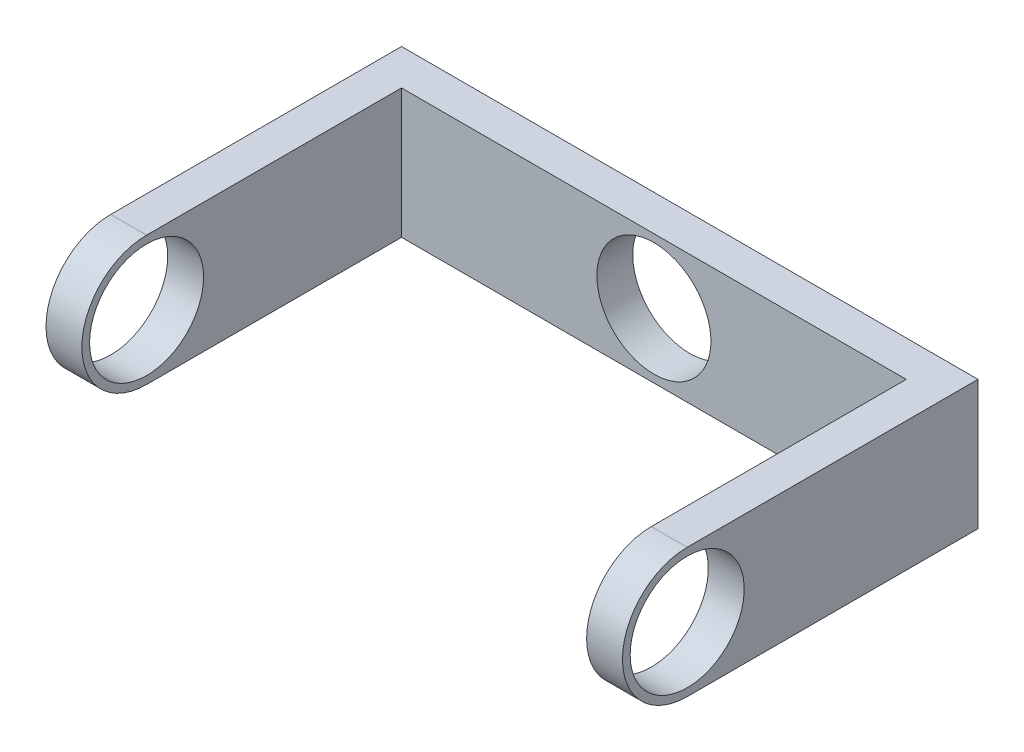
SolidWorks part; units mm, degrees
ref_plane "Front Plane" through (0, 0, 0) normal (0, 0, 1) x (1, 0, 0)
ref_plane "Top Plane" through (0, 0, 0) normal (0, 1, 0) x (1, 0, 0)
ref_plane "Right Plane" through (0, 0, 0) normal (1, 0, 0) x (0, 0, -1)
sketch "Sketch1" plane through (0, 0, 0) normal (0, 1, 0) x (1, 0, 0)
  line L0 (-56.25, 0) -> (56.25, 0) construction
  line L1 (-56.25, 11.125) -> (-56.25, -11.125)
  line L2 (-49.25, 11.125) -> (-49.25, -11.125)
  line L3 (-56.25, -11.125) -> (-49.25, -11.125)
  line L4 (-56.25, 11.125) -> (-49.25, 11.125)
  line L5 (0, 0) -> (0, 56.25) construction
  line L6 (56.25, 56.25) -> (-56.25, 56.25)
  line L7 (-56.25, 56.25) -> (-56.25, 11.125)
  line L8 (-49.25, 11.125) -> (-49.25, 49.25)
  line L9 (56.25, 11.125) -> (49.25, 11.125)
  line L10 (49.25, 11.125) -> (49.25, -11.125)
  line L11 (56.25, -11.125) -> (49.25, -11.125)
  line L12 (56.25, 11.125) -> (56.25, -11.125)
  line L13 (49.25, 11.125) -> (49.25, 49.25)
  line L14 (56.25, 56.25) -> (56.25, 11.125)
  line L15 (-49.25, 49.25) -> (49.25, 49.25)
  line L16 (-56.25, -11.125) -> (-56.25, -13.125)
  line L17 (-56.25, -13.125) -> (-49.25, -13.125)
  line L18 (-49.25, -13.125) -> (-49.25, -11.125)
  line L19 (49.25, -13.125) -> (49.25, -11.125)
  line L20 (56.25, -13.125) -> (49.25, -13.125)
  line L21 (56.25, -11.125) -> (56.25, -13.125)
  circle A0 centre (0, 0) radius 44.45 construction
  point P5 (0, 0)
  point P9 (-56.25, 0)
  point P15 (0, 56.25)
  dimension "D1" = 88.9
  dimension "D2" = 112.5
  dimension "D3" = 22.25
  dimension "D5" = 56.25
  dimension "D6" = 7
  dimension "D7" = 7
  dimension "D8" = 2
  dimension "D4" = 2
extrude "Boss-Extrude1" add sketch "Sketch1" along normal mid plane 25.25 contours L17 L18 L3 L16 | L4 L1 L3 L2 | L8 L15 L13 L9 L14 L6 L7 L4 | L12 L9 L10 L11 | L21 L11 L19 L20 region at (-52.75, 0, 0) region at (-55.0379, 0, -33.6875) region at (-52.75, 0, 12.125) region at (52.75, 0, 0) region at (52.75, 0, 12.125)
sketch "Sketch2" plane through (-56.25, 0, 0) normal (-1, 0, 0) x (0, 0, 1)
  line L0 (13.125, 12.625) -> (13.125, -12.625) construction
  line L1 (-56.25, 12.625) -> (13.125, 12.625) construction
  line L2 (-56.25, -12.625) -> (13.125, -12.625) construction
  line L3 (0.5, 12.625) -> (13.125, 12.625)
  line L4 (13.125, 12.625) -> (13.125, -12.625)
  line L5 (13.125, -12.625) -> (0.5, -12.625)
  circle A0 centre (0.5, 0) radius 12.625
  circle A1 centre (0.5, 0) radius 11.125
  line M1 (-56.25, -12.625) -> (13.125, -12.625)
  line M2 (13.125, -12.625) -> (13.125, 12.625)
  line M3 (13.125, 12.625) -> (-56.25, 12.625)
  dimension "D1" = 22.25
extrude "Cut-Extrude1" cut sketch "Sketch2" against normal through all both and the other way through all contours A1 | A0 L4 M3 | A0 M1 M2 region at (-56.25, 9.805, 10.305) region at (-56.25, -9.805, 10.305) region at (-56.25, 0, 0.5)
sketch "Sketch3" plane through (0, 0, -56.25) normal (0, 0, -1) x (-1, 0, 0)
  circle A0 centre (0, 0) radius 11.125
  dimension "D1" = 22.25
extrude "Cut-Extrude2" cut sketch "Sketch3" against normal up to surface (7 mm away) up to face at (0, 0, -49.25)
